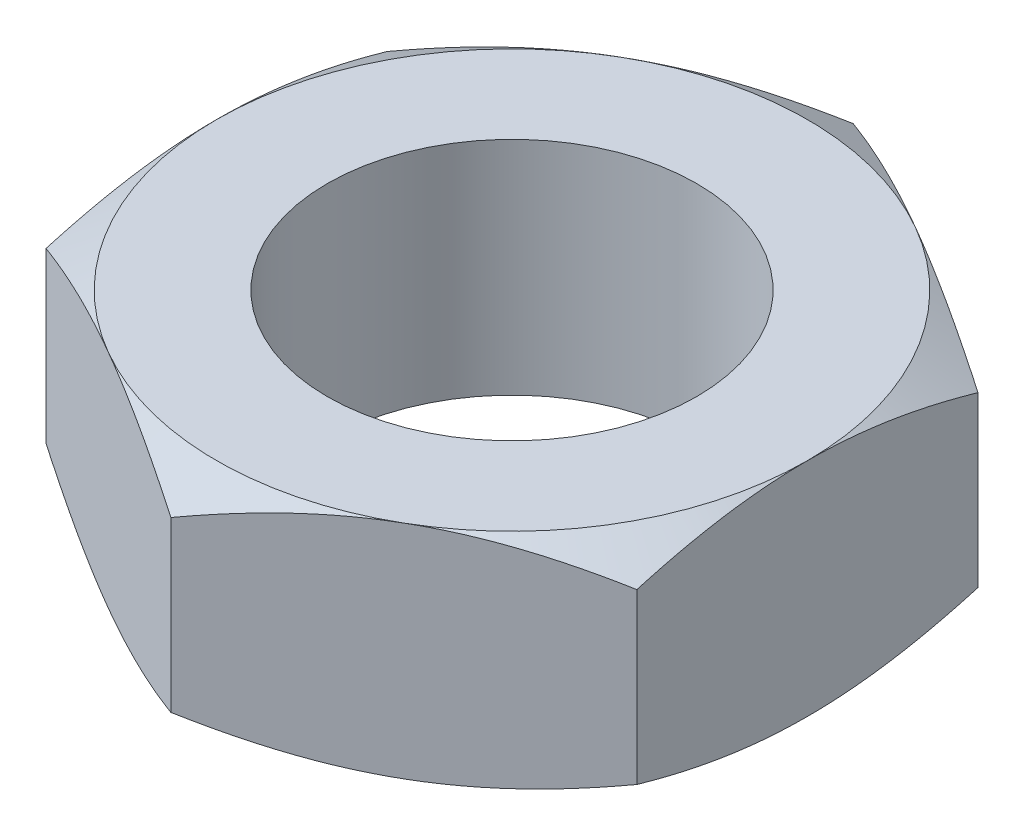
SolidWorks part; units mm, degrees
material "Alloy Steel"
ref_plane "Front Plane" through (0, 0, 0) normal (0, 0, 1) x (1, 0, 0)
ref_plane "Top Plane" through (0, 0, 0) normal (0, 1, 0) x (1, 0, 0)
ref_plane "Right Plane" through (0, 0, 0) normal (1, 0, 0) x (0, 0, -1)
sketch "Sketch1" plane through (0, 0, 0) normal (0, 1, 0) x (1, 0, 0)
  line L1 (-6.35, 3.6662) -> (-6.35, -3.6662)
  line L2 (-6.35, -3.6662) -> (0, -7.3323)
  line L3 (0, -7.3323) -> (6.35, -3.6662)
  line L4 (6.35, -3.6662) -> (6.35, 3.6662)
  line L5 (6.35, 3.6662) -> (0, 7.3323)
  line L6 (0, 7.3323) -> (-6.35, 3.6662)
  circle A0 centre (0, 0) radius 6.35 construction
  circle A1 centre (0, 0) radius 3.9688
  dimension "Thread Size" = 7.9375
  dimension "Hex" = 12.7
extrude "Boss-Extrude1" add sketch "Sketch1" along normal mid plane 4.7625
sketch "Sketch2" plane through (0, 2.3813, 0) normal (0, 1, 0) x (1, 0, 0)
  circle A0 centre (0, 0) radius 3.9688 construction
  circle A1 centre (0, 0) radius 3.9688
curve "Helix/Spiral1" [suppressed] pitch 1.0583 height 5.8208 turns 5.5 parameters "Pitch"=1.0583
sketch "Sketch3" plane through (0, 0, 0) normal (1, 0, 0) x (0, 0, -1)
  line L0 (3.2813, 2.9104) -> (3.9688, 3.3073)
  line L1 (3.9688, 3.3073) -> (3.9688, 2.3813)
  line L2 (3.9688, 2.3813) -> (3.2813, 2.7781)
  line L3 (3.2813, 2.7781) -> (3.2813, 2.9104)
  line L4 (3.625, 3.1089) -> (3.625, 2.5797) construction
  line L5 (3.2813, 2.8443) -> (3.9688, 2.8443) construction
  line L6 (3.9688, 2.3813) -> (-3.9688, 2.3813) construction
  dimension "D1" = 60
  dimension "D2" = 0.1323
  dimension "D3" = 0.5292
sweep "Sweep1" [suppressed] add profiles "Sketch3" path "Helix/Spiral1"
sketch "Sketch4" plane through (0, 2.3813, 0) normal (0, 1, 0) x (1, 0, 0)
  circle A1 centre (0, 0) radius 3.9688
  circle A2 centre (0, 0) radius 3.9688
  dimension "D1" = 0
extrude "Cut-Extrude1" [suppressed] cut sketch "Sketch4" along normal through all and the other way through all draft 45
sketch "Sketch5" plane through (0, 2.3813, 0) normal (0, 1, 0) x (1, 0, 0)
  circle A0 centre (0, 0) radius 6.35 construction
  circle A1 centre (0, 0) radius 6.35
extrude "Cut-Extrude2" cut sketch "Sketch5" against normal through all draft 60 flip side to cut
mirror "Mirror1" about plane through (0, 0, 0) normal (0, 1, 0) of "Cut-Extrude2", "Cut-Extrude1"
equation "\"D2@Sketch3\" = \"Pitch@Helix/Spiral1\"*.125"
equation "\"D3@Sketch3\" = \"Pitch@Helix/Spiral1\"*.5"
equation "\"D3@Helix/Spiral1\" = \"Height@Boss-Extrude1\"+\"Pitch@Helix/Spiral1\""
